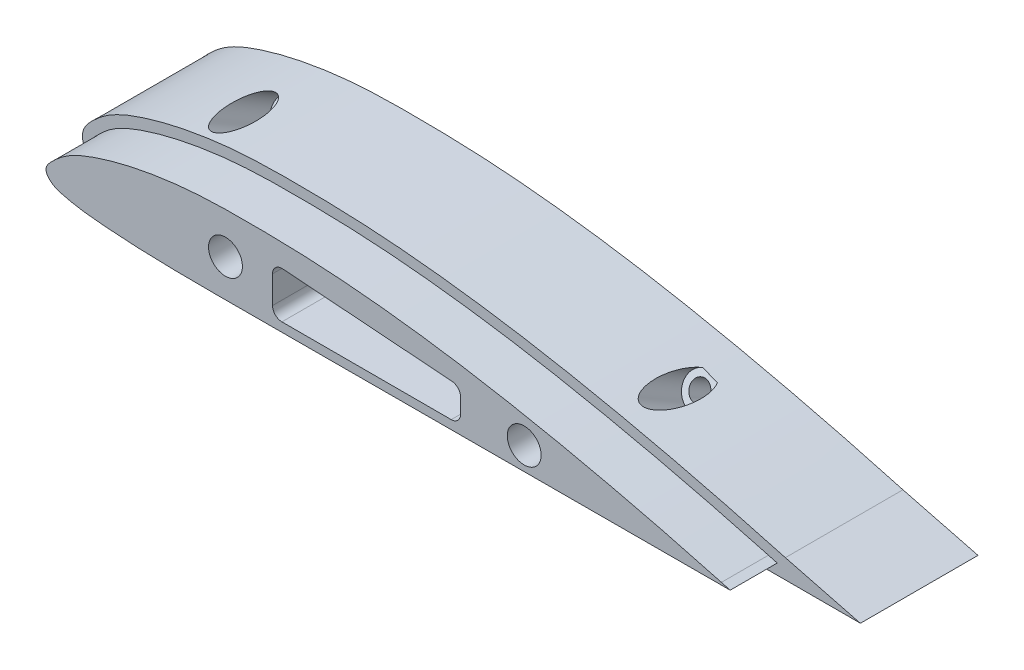
SolidWorks part; units mm, degrees
ref_plane "Front Plane" through (0, 0, 0) normal (0, 0, 1) x (1, 0, 0)
ref_plane "Top Plane" through (0, 0, 0) normal (0, 1, 0) x (1, 0, 0)
ref_plane "Right Plane" through (0, 0, 0) normal (1, 0, 0) x (0, 0, -1)
sketch "Sketch1" plane through (0, 0, 0) normal (0, 0, 1) x (1, 0, 0)
  line L4 (283.5115, 5) -> (300, 5)
  line L5 (300, 5) -> (284.0429, 9.1047)
  spline S2 degree 3 poles (284.0429, 9.1047) (281.0182, 9.9344) (274.9702, 11.5879) (262.7947, 14.6943) (247.4912, 18.2235) (228.9768, 21.8279) (213.3822, 24.0502) (200.838, 25.2782) (191.3752, 25.8437) (181.9292, 26.0327) (174.0455, 26.006) (167.6846, 25.6725) (162.9071, 25.1908) (158.1715, 24.4731) (154.2495, 23.6877) (151.1262, 22.9144) (148.8034, 22.2534) (146.5027, 21.5203) (144.1955, 20.6739) (142.2855, 19.8254) (140.7789, 19.0238) (139.6571, 18.333) (138.5799, 17.556) (137.5736, 16.6946) (136.8402, 16.0177) (136.1979, 15.3779) (135.7035, 14.8191) (135.2097, 14.1357) (134.8343, 13.4013) (134.6172, 12.6132) (134.5644, 11.9259) (134.6325, 11.2839) (134.8239, 10.646) (135.0503, 10.1715) (135.4024, 9.5941) (135.889, 9.014) (136.5032, 8.4537) (137.1891, 7.9612) (137.9344, 7.5673) (138.8878, 7.188) (139.9999, 6.8937) (141.1193, 6.6336) (142.3398, 6.3625) (143.5667, 6.1418) (145.2014, 5.9056) (147.2085, 5.702) (149.5549, 5.5018) (152.7201, 5.2635) (156.6645, 5.0546) (161.3946, 4.9004) (166.1151, 4.8221) (170.8269, 4.7935) (175.5318, 4.7968) (181.7926, 4.8194) (189.6121, 4.8333) (199.0042, 4.8461) (208.3936, 4.8645) (217.7834, 4.8816) (230.303, 4.9047) (245.9523, 4.9321) (264.7317, 4.9664) (277.2516, 4.9881) (283.5115, 5) knots 0 0 0 0 0.03125 0.0625 0.125 0.1875 0.25 0.28125 0.3125 0.34375 0.375 0.390625 0.40625 0.421875 0.4375 0.445312 0.453125 0.460938 0.46875 0.476562 0.480469 0.484375 0.488281 0.492188 0.496094 0.498047 0.5 0.501953 0.503906 0.504883 0.505859 0.506836 0.507812 0.508789 0.509766 0.511719 0.513672 0.515625 0.517578 0.519531 0.523438 0.527344 0.53125 0.535156 0.539062 0.546875 0.554688 0.5625 0.578125 0.59375 0.609375 0.625 0.640625 0.65625 0.6875 0.71875 0.75 0.78125 0.8125 0.875 0.9375 1 1 1 1
extrude "Boss-Extrude1" add sketch "Sketch1" along normal blind 25
sketch "Sketch2" plane through (0, 0, 25) normal (0, 0, 1) x (1, 0, 0)
  line L0 (283.5138, 7.176) -> (283.5077, 7)
  spline S1 degree 3 poles (283.5138, 7.176) (281.5719, 7.7087) (278.6602, 8.5075) (273.8037, 9.8057) (267.9783, 11.312) (262.1421, 12.7496) (255.3336, 14.3496) (248.5296, 15.8732) (237.8298, 18.0745) (225.1769, 20.3734) (211.4981, 22.2445) (201.7081, 23.1823) (192.8989, 23.7583) (187.0194, 23.95) (180.1574, 24.0138) (175.2497, 24.0043) (170.3385, 23.8312) (165.4154, 23.4617) (161.4718, 22.9737) (156.5308, 22.1318) (152.5638, 21.2602) (148.6188, 20.1142) (145.6144, 19.0989) (143.118, 18.0296) (141.124, 16.9205) (139.7091, 15.9185) (138.6393, 14.9581) (137.8213, 14.1846) (137.2992, 13.6166) (136.9099, 13.0649) (136.6947, 12.6285) (136.5581, 12.111) (136.5906, 11.6817) (136.7264, 11.3043) (136.876, 11.0027) (137.1856, 10.5599) (137.6647, 10.0852) (138.4186, 9.5356) (139.4995, 9.074) (140.8875, 8.7436) (142.3453, 8.4004) (143.8077, 8.1247) (145.7594, 7.8486) (148.2057, 7.6221) (151.1393, 7.3799) (157.0097, 7.007) (166.8124, 6.7551) (180.539, 6.8235) (193.287, 6.8363) (208.9776, 6.8654) (224.6681, 6.8944) (240.3587, 6.9228) (251.1459, 6.9412) (259.9719, 6.958) (268.7978, 6.973) (276.6431, 6.9879) (281.5464, 6.9963) (283.5077, 7) knots 0 0 0 0 0.020105 0.030145 0.050191 0.08018 0.090156 0.12002 0.149793 0.199219 0.248396 0.287604 0.297393 0.336535 0.346322 0.365908 0.385531 0.395376 0.415192 0.425184 0.445412 0.455711 0.466191 0.477055 0.482787 0.488946 0.494316 0.497126 0.500187 0.502001 0.50385 0.50502 0.507318 0.507987 0.509024 0.510668 0.513358 0.515716 0.519949 0.524973 0.529954 0.534903 0.539824 0.54963 0.559425 0.569214 0.608356 0.657307 0.706263 0.735637 0.813967 0.862923 0.892297 0.92167 0.951044 0.980418 1 1 1 1
extrude "Boss-Extrude2" add sketch "Sketch2" along normal blind 10
sketch "Sketch4" plane through (0, 0, 35) normal (0, 0, 1) x (1, 0, 0)
  line L0 (300, 5) -> (88.4314, 5) construction
  circle A0 centre (175, 15) radius 3.6
  circle A1 centre (238.5138, 12) radius 3.6
  dimension "D2" = 125
  dimension "D3" = 45
  dimension "D4" = 7
  dimension "D1" = 10
extrude "Cut-Extrude1" cut sketch "Sketch4" against normal blind 15 contours A0 | A1
sketch "Sketch5" plane through (0, 0, 35) normal (0, 0, 1) x (1, 0, 0)
  line L0 (185, 19) -> (185, 9)
  line L1 (185, 9) -> (225, 9)
  line L2 (225, 9) -> (225, 16)
  line L3 (225, 16) -> (185, 19)
  line L4 (300, 5) -> (100, 5) construction
  dimension "D1" = 10
  dimension "D2" = 4
  dimension "D3" = 7
  dimension "D4" = 75
  dimension "D5" = 40
extrude "Cut-Extrude3" cut sketch "Sketch5" against normal through all
fillet "Fillet1" radius 2 4 edges at (185, 19, 17.5) (185, 9, 17.5) (225, 16, 17.5) (225, 9, 17.5)
sketch "Sketch7" plane through (0, 0, 20) normal (0, 0, 1) x (1, 0, 0)
  circle A0 centre (238.5138, 12) radius 3.6 construction
  circle A1 centre (238.5138, 12) radius 3.6
  circle A2 centre (175, 15) radius 3.6
extrude "Cut-Extrude5" cut sketch "Sketch7" against normal blind 10
ref_plane "Plane1" through (160, 0, 0) normal (1, 0, 0) x (0, 0, -1)
sketch "Sketch8" plane through (160, 0, 0) normal (1, 0, 0) x (0, 0, -1)
  line L0 (-28.294, 31.7375) -> (0, 15.4019)
  line L2 (0, 4.7961) -> (0, 26.0077) construction
  line L3 (0, 15.4019) -> (-20.6135, 15.4019) construction
  dimension "D1" = 30
ref_plane "Plane2" through (160, 31.7375, 28.294) normal (0, -0.5, -0.866) x (-1, 0, 0)
sketch "Sketch9" plane through (160, 31.7375, 28.294) normal (0, -0.5, -0.866) x (-1, 0, 0)
  line L0 (0, 0) -> (0, -10.3067) construction
  line L1 (0, 0) -> (0, -5) construction
  line L2 (0, -5) -> (-90, -5) construction
  circle A0 centre (0, 0) radius 2.1
  circle A1 centre (-90, -5) radius 2.1
extrude "Cut-Extrude6" cut sketch "Sketch9" along normal through all
sketch "Sketch10" plane through (160, 31.7375, 28.294) normal (0, -0.5, -0.866) x (-1, 0, 0)
  circle A0 centre (0, 0) radius 3.5
  circle A1 centre (-90, -5) radius 3.5
extrude "Cut-Extrude7" cut sketch "Sketch10" along normal blind 25 contours A1 | A0
sketch "Sketch11" plane through (0, 0, 35) normal (0, 0, 1) x (1, 0, 0)
  line L0 (280.5134, 7.2445) -> (282.3112, 7.2477)
  line L3 (280.448, 7.7565) -> (282.3112, 7.2477)
  line L6 (283.5115, 5) -> (300, 5)
  line L7 (300, 5) -> (284.0429, 9.1047)
  line L8 (283.5115, 5) -> (300, 5)
  line L9 (300, 5) -> (284.0429, 9.1047)
  spline S2 degree 3 poles (2469.1253, 3330.2831) (578.7241, -152.5431) (439.4264, -30.371) (262.7947, 14.6943) (247.4912, 18.2235) (228.9768, 21.8279) (213.3822, 24.0502) (200.838, 25.2782) (191.3752, 25.8437) (181.9292, 26.0327) (174.0455, 26.006) (167.6846, 25.6725) (162.9071, 25.1908) (158.1715, 24.4731) (154.2495, 23.6877) (151.1262, 22.9144) (148.8034, 22.2534) (146.5027, 21.5203) (144.1955, 20.6739) (142.2855, 19.8254) (140.7789, 19.0238) (139.6571, 18.333) (138.5799, 17.556) (137.5736, 16.6946) (136.8402, 16.0177) (136.1979, 15.3779) (135.7035, 14.8191) (135.2097, 14.1357) (134.8343, 13.4013) (134.6172, 12.6132) (134.5644, 11.9259) (134.6325, 11.2839) (134.8239, 10.646) (135.0503, 10.1715) (135.4024, 9.5941) (135.889, 9.014) (136.5032, 8.4537) (137.1891, 7.9612) (137.9344, 7.5673) (138.8878, 7.188) (139.9999, 6.8937) (141.1193, 6.6336) (142.3398, 6.3625) (143.5667, 6.1418) (145.2014, 5.9056) (147.2085, 5.702) (149.5549, 5.5018) (152.7201, 5.2635) (156.6645, 5.0546) (161.3946, 4.9004) (166.1151, 4.8221) (170.8269, 4.7935) (175.5318, 4.7968) (181.7926, 4.8194) (189.6121, 4.8333) (199.0042, 4.8461) (208.3936, 4.8645) (217.7834, 4.8816) (230.303, 4.9047) (245.9523, 4.9321) (1062.3632, 6.4244) (1873.6845, 2.8543) (2454.3014, 2917.181) knots -1.688391 -1.688391 -1.688391 -1.688391 0.03125 0.0625 0.125 0.1875 0.25 0.28125 0.3125 0.34375 0.375 0.390625 0.40625 0.421875 0.4375 0.445312 0.453125 0.460938 0.46875 0.476562 0.480469 0.484375 0.488281 0.492188 0.496094 0.498047 0.5 0.501953 0.503906 0.504883 0.505859 0.506836 0.507812 0.508789 0.509766 0.511719 0.513672 0.515625 0.517578 0.519531 0.523438 0.527344 0.53125 0.535156 0.539062 0.546875 0.554688 0.5625 0.578125 0.59375 0.609375 0.625 0.640625 0.65625 0.6875 0.71875 0.75 0.78125 0.8125 0.875 0.9375 8.963818 8.963818 8.963818 8.963818 only from (284.0429, 9.1047) to (283.5115, 5)
  spline S3 degree 3 poles (280.448, 7.7565) (274.5345, 9.3714) (262.6663, 12.4565) (244.7251, 16.5) (229.6665, 19.3599) (217.5457, 21.1803) (208.4198, 22.2922) (199.2672, 23.1416) (190.0905, 23.6336) (180.8981, 23.7894) (173.2386, 23.7336) (167.1292, 23.3697) (162.5678, 22.8749) (158.0342, 22.1607) (153.5392, 21.2365) (149.8525, 20.2348) (146.9452, 19.2923) (144.8035, 18.4896) (142.7255, 17.5469) (141.0857, 16.5987) (139.8698, 15.7033) (139.0136, 14.961) (138.1704, 14.1822) (137.4011, 13.3736) (136.8033, 12.4442) (136.8299, 11.4518) (137.4826, 10.5655) (138.3295, 9.8695) (139.3297, 9.4073) (140.4153, 9.1074) (141.5373, 8.8472) (143.0221, 8.5123) (144.8994, 8.2037) (147.177, 7.9637) (149.4676, 7.7672) (152.5195, 7.5313) (156.3422, 7.3214) (160.9342, 7.1629) (165.53, 7.0792) (171.6595, 7.0342) (179.3241, 7.0622) (188.5242, 7.0825) (197.7228, 7.0937) (209.9881, 7.1177) (225.3196, 7.1455) (243.7176, 7.1784) (262.1155, 7.2115) (274.3808, 7.2336) (280.5134, 7.2445) knots 0.010352 0.010352 0.010352 0.010352 0.071582 0.132813 0.194043 0.224658 0.255273 0.285888 0.316503 0.347118 0.377734 0.393041 0.408349 0.423656 0.438964 0.454271 0.461925 0.469579 0.477233 0.484887 0.488713 0.49254 0.496367 0.500194 0.504021 0.507848 0.511675 0.515502 0.519329 0.523155 0.526982 0.530809 0.538463 0.546117 0.553771 0.561424 0.576732 0.592039 0.607347 0.622655 0.65327 0.683885 0.7145 0.745115 0.806345 0.867576 0.928806 0.990036 0.990036 0.990036 0.990036
  spline S4 degree 3 poles (284.0429, 9.1047) (281.0182, 9.9344) (274.9702, 11.5879) (262.7947, 14.6943) (247.4912, 18.2235) (228.9768, 21.8279) (213.3822, 24.0502) (200.838, 25.2782) (191.3752, 25.8437) (181.9292, 26.0327) (174.0455, 26.006) (167.6846, 25.6725) (162.9071, 25.1908) (158.1715, 24.4731) (154.2495, 23.6877) (151.1262, 22.9144) (148.8034, 22.2534) (146.5027, 21.5203) (144.1955, 20.6739) (142.2855, 19.8254) (140.7789, 19.0238) (139.6571, 18.333) (138.5799, 17.556) (137.5736, 16.6946) (136.8402, 16.0177) (136.1979, 15.3779) (135.7035, 14.8191) (135.2097, 14.1357) (134.8343, 13.4013) (134.6172, 12.6132) (134.5644, 11.9259) (134.6325, 11.2839) (134.8239, 10.646) (135.0503, 10.1715) (135.4024, 9.5941) (135.889, 9.014) (136.5032, 8.4537) (137.1891, 7.9612) (137.9344, 7.5673) (138.8878, 7.188) (139.9999, 6.8937) (141.1193, 6.6336) (142.3398, 6.3625) (143.5667, 6.1418) (145.2014, 5.9056) (147.2085, 5.702) (149.5549, 5.5018) (152.7201, 5.2635) (156.6645, 5.0546) (161.3946, 4.9004) (166.1151, 4.8221) (170.8269, 4.7935) (175.5318, 4.7968) (181.7926, 4.8194) (189.6121, 4.8333) (199.0042, 4.8461) (208.3936, 4.8645) (217.7834, 4.8816) (230.303, 4.9047) (245.9523, 4.9321) (264.7317, 4.9664) (277.2516, 4.9881) (283.5115, 5) knots 0 0 0 0 0.03125 0.0625 0.125 0.1875 0.25 0.28125 0.3125 0.34375 0.375 0.390625 0.40625 0.421875 0.4375 0.445312 0.453125 0.460938 0.46875 0.476562 0.480469 0.484375 0.488281 0.492188 0.496094 0.498047 0.5 0.501953 0.503906 0.504883 0.505859 0.506836 0.507812 0.508789 0.509766 0.511719 0.513672 0.515625 0.517578 0.519531 0.523438 0.527344 0.53125 0.535156 0.539062 0.546875 0.554688 0.5625 0.578125 0.59375 0.609375 0.625 0.640625 0.65625 0.6875 0.71875 0.75 0.78125 0.8125 0.875 0.9375 1 1 1 1
  dimension "D1" = 0
extrude "Cut-Extrude8" cut sketch "Sketch11" against normal up to surface (10 mm away) up to face at (289.2734, 7.0524, 25)
